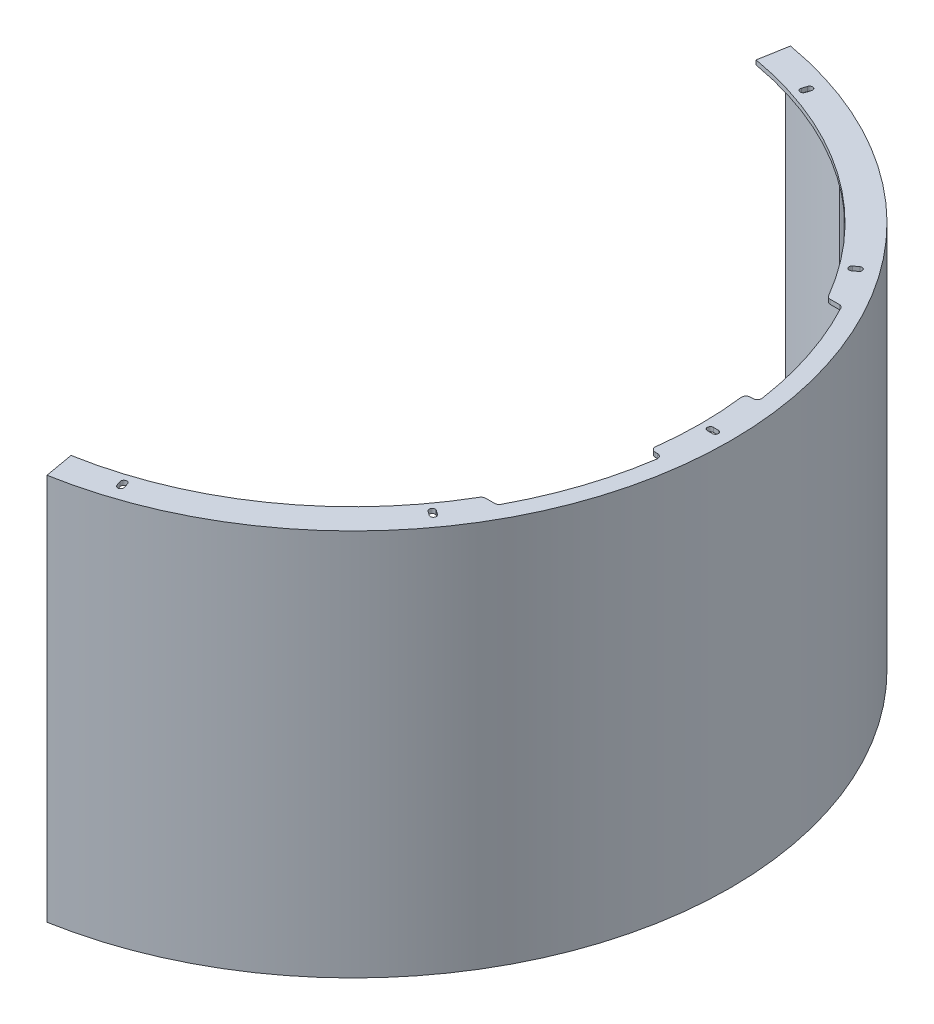
SolidWorks part; units mm, degrees
ref_plane "Front Plane" through (0, 0, 0) normal (0, 0, 1) x (1, 0, 0)
ref_plane "Top Plane" through (0, 0, 0) normal (0, 1, 0) x (1, 0, 0)
ref_plane "Right Plane" through (0, 0, 0) normal (1, 0, 0) x (0, 0, -1)
sketch "Sketch3" plane through (0, 0, 0) normal (0, 1, 0) x (1, 0, 0)
  line L0 (0, -251.5) -> (0, 251.5)
  line L1 (-44.1935, 250.6336) -> (-43.6725, 247.6791)
  line L2 (-43.6725, -247.6791) -> (-44.1935, -250.6336)
  arc A0 (0, 251.5) -> (0, -251.5) centre (0, 0) cw
  arc A1 (0, 251.5) -> (-43.6725, 247.6791) centre (0, 0) ccw
  arc A2 (0, -251.5) -> (-43.6725, -247.6791) centre (0, 0) cw
  arc A3 (0, 254.5) -> (0, -254.5) centre (0, 0) cw
  arc A4 (0, 254.5) -> (-44.1935, 250.6336) centre (0, 0) ccw
  arc A5 (0, -254.5) -> (-44.1935, -250.6336) centre (0, 0) cw
  point P4 (0, 0)
  dimension "D1" = 503
  dimension "D2" = 3
  dimension "D3" = 3
  dimension "D4" = 3
extrude "Boss-Extrude1" add sketch "Sketch3" along normal blind 255 contours A5 A3 A4 L1 A1 A0 A2 L2 region at (252.0902, 0, 0)
sketch "Sketch6" plane through (0, 255, 0) normal (0, 1, 0) x (1, 0, 0)
  line L0 (0, -256) -> (0, 256)
  line L1 (-2, 253.0819) -> (-2, 247.0819)
  line L2 (-1, 246.0819) -> (1, 246.0819)
  line L3 (2, 247.0819) -> (2, 253.0819)
  line L4 (-2, 253.0819) -> (2, 253.0819)
  line L54 (108.0062, 228.8867) -> (105.4029, 223.4809)
  line L55 (105.87, 222.146) -> (107.6719, 221.2783)
  line L56 (109.0068, 221.7454) -> (111.6101, 227.1512)
  line L57 (108.0062, 228.8867) -> (111.6101, 227.1512)
  line L58 (196.6204, 159.3577) -> (191.9294, 155.6167)
  line L59 (191.7711, 154.2114) -> (193.0181, 152.6477)
  line L60 (194.4234, 152.4894) -> (199.1144, 156.2303)
  line L61 (196.6204, 159.3577) -> (199.1144, 156.2303)
  line L62 (246.2916, 58.2659) -> (240.442, 56.9308)
  line L63 (239.6896, 55.7333) -> (240.1347, 53.7835)
  line L64 (241.3321, 53.031) -> (247.1817, 54.3662)
  line L65 (246.2916, 58.2659) -> (247.1817, 54.3662)
  line L66 (247.1817, -54.3662) -> (241.3321, -53.031)
  line L67 (240.1347, -53.7835) -> (239.6896, -55.7333)
  line L68 (240.442, -56.9308) -> (246.2916, -58.2659)
  line L69 (247.1817, -54.3662) -> (246.2916, -58.2659)
  line L70 (199.1144, -156.2303) -> (194.4234, -152.4894)
  line L71 (193.0181, -152.6477) -> (191.7711, -154.2114)
  line L72 (191.9294, -155.6167) -> (196.6204, -159.3577)
  line L73 (199.1144, -156.2303) -> (196.6204, -159.3577)
  line L74 (111.6101, -227.1512) -> (109.0068, -221.7454)
  line L75 (107.6719, -221.2783) -> (105.87, -222.146)
  line L76 (105.4029, -223.4809) -> (108.0062, -228.8867)
  line L77 (111.6101, -227.1512) -> (108.0062, -228.8867)
  line L78 (2, -253.0819) -> (2, -247.0819)
  line L79 (1, -246.0819) -> (-1, -246.0819)
  line L80 (-2, -247.0819) -> (-2, -253.0819)
  line L81 (2, -253.0819) -> (-2, -253.0819)
  arc A2 (2, 247.0819) -> (1, 246.0819) centre (1, 247.0819) cw
  arc A3 (-2, 247.0819) -> (-1, 246.0819) centre (-1, 247.0819) ccw
  arc A26 (109.0068, 221.7454) -> (107.6719, 221.2783) centre (108.1058, 222.1792) cw
  arc A27 (105.4029, 223.4809) -> (105.87, 222.146) centre (106.3039, 223.047) ccw
  arc A28 (194.4234, 152.4894) -> (193.0181, 152.6477) centre (193.7999, 153.2712) cw
  arc A29 (191.9294, 155.6167) -> (191.7711, 154.2114) centre (192.5529, 154.8349) ccw
  arc A30 (241.3321, 53.031) -> (240.1347, 53.7835) centre (241.1096, 54.006) cw
  arc A31 (240.442, 56.9308) -> (239.6896, 55.7333) centre (240.6645, 55.9558) ccw
  arc A32 (240.442, -56.9308) -> (239.6896, -55.7333) centre (240.6645, -55.9558) cw
  arc A33 (241.3321, -53.031) -> (240.1347, -53.7835) centre (241.1096, -54.006) ccw
  arc A34 (191.9294, -155.6167) -> (191.7711, -154.2114) centre (192.5529, -154.8349) cw
  arc A35 (194.4234, -152.4894) -> (193.0181, -152.6477) centre (193.7999, -153.2712) ccw
  arc A36 (105.4029, -223.4809) -> (105.87, -222.146) centre (106.3039, -223.047) cw
  arc A37 (109.0068, -221.7454) -> (107.6719, -221.2783) centre (108.1058, -222.1792) ccw
  arc A38 (-2, -247.0819) -> (-1, -246.0819) centre (-1, -247.0819) cw
  arc A39 (2, -247.0819) -> (1, -246.0819) centre (1, -247.0819) ccw
  point P9 (0, 0)
  point P19 (2, 246.0819)
  point P22 (-2, 246.0819)
  point P23 (0, 246.0819)
  point P59 (0, 0)
  point P68 (0, 0)
  point P76 (0, 0)
  dimension "D3" = 1
  dimension "D1" = 7
  dimension "D2" = 4
  dimension "D4" = 0
  dimension "D5" = 7
  dimension "D6" = 256
  dimension "D7" = 8
extrude "Boss-Extrude2" add sketch "Sketch6" against normal blind 255 separate body contours L3 L4 L1 A3 L2 A2 | L56 L57 L54 A27 L55 A26 | L60 L61 L58 A29 L59 A28 | L64 L65 L62 A31 L63 A30 | L68 L69 L66 A33 L67 A32 | L72 L73 L70 A35 L71 A34 | L76 L77 L74 A37 L75 A36 | L78 A39 L79 A38 L80 L81
combine bodies "Combine2" operation type add bodies to combine 109 101 115 116 117 118 119 120 121
sketch "Sketch7" plane through (0, 255, 0) normal (0, 1, 0) x (1, 0, 0)
  line L0 (-44.1935, 250.6336) -> (-40.7205, 230.9374)
  line L1 (-44.1935, -250.6336) -> (-40.7205, -230.9374)
  arc A0 (-40.7205, 230.9374) -> (-40.7205, -230.9374) centre (0, 0) cw
  arc A2 (-44.1935, 250.6336) -> (-44.1935, -250.6336) centre (0, 0) cw
  arc A3 (-44.1935, -250.6336) -> (-44.1935, 250.6336) centre (0, 0) ccw construction
extrude "Boss-Extrude3" add sketch "Sketch7" along normal blind 3 contours A2 L0 A0 L1 region at (248.5983, 255, 0)
sketch "Sketch8" plane through (0, 255, 0) normal (0, -1, 0) x (1, 0, 0)
  line L0 (240.8, 0) -> (244.2, 0) construction
  line L1 (240.8, 2) -> (244.2, 2)
  line L2 (240.8, -2) -> (244.2, -2)
  line L3 (194.8113, -141.5387) -> (197.562, -143.5372) construction
  line L12 (195.9869, -139.9207) -> (198.7375, -141.9191)
  line L21 (193.6357, -143.1567) -> (196.3864, -145.1552)
  line L24 (74.4113, -229.0144) -> (75.462, -232.248) construction
  line L27 (76.3134, -228.3964) -> (77.3641, -231.63)
  line L28 (72.5092, -229.6324) -> (73.5598, -232.866)
  line L29 (-74.4113, -229.0144) -> (-75.462, -232.248) construction
  line L30 (-72.5092, -229.6324) -> (-73.5598, -232.866)
  line L31 (-76.3134, -228.3964) -> (-77.3641, -231.63)
  line L32 (-194.8113, -141.5387) -> (-197.562, -143.5372) construction
  line L33 (-193.6357, -143.1567) -> (-196.3864, -145.1552)
  line L34 (-195.9869, -139.9207) -> (-198.7375, -141.9191)
  line L35 (-240.8, 0) -> (-244.2, 0) construction
  line L36 (-240.8, -2) -> (-244.2, -2)
  line L37 (-240.8, 2) -> (-244.2, 2)
  line L38 (-194.8113, 141.5387) -> (-197.562, 143.5372) construction
  line L39 (-195.9869, 139.9207) -> (-198.7375, 141.9191)
  line L40 (-193.6357, 143.1567) -> (-196.3864, 145.1552)
  line L41 (-74.4113, 229.0144) -> (-75.462, 232.248) construction
  line L42 (-76.3134, 228.3964) -> (-77.3641, 231.63)
  line L43 (-72.5092, 229.6324) -> (-73.5598, 232.866)
  line L44 (74.4113, 229.0144) -> (75.462, 232.248) construction
  line L45 (72.5092, 229.6324) -> (73.5598, 232.866)
  line L46 (76.3134, 228.3964) -> (77.3641, 231.63)
  line L47 (194.8113, 141.5387) -> (197.562, 143.5372) construction
  line L48 (193.6357, 143.1567) -> (196.3864, 145.1552)
  line L49 (195.9869, 139.9207) -> (198.7375, 141.9191)
  circle A1 centre (242.5, 0) radius 1.7 construction
  arc A2 (240.8, 2) -> (240.8, -2) centre (240.8, 0) ccw
  arc A3 (244.2, -2) -> (244.2, 2) centre (244.2, 0) ccw
  arc A24 (195.9869, -139.9207) -> (193.6357, -143.1567) centre (194.8113, -141.5387) ccw
  arc A25 (196.3864, -145.1552) -> (198.7375, -141.9191) centre (197.562, -143.5372) ccw
  arc A26 (76.3134, -228.3964) -> (72.5092, -229.6324) centre (74.4113, -229.0144) ccw
  arc A27 (73.5598, -232.866) -> (77.3641, -231.63) centre (75.462, -232.248) ccw
  arc A28 (-72.5092, -229.6324) -> (-76.3134, -228.3964) centre (-74.4113, -229.0144) ccw
  arc A29 (-77.3641, -231.63) -> (-73.5598, -232.866) centre (-75.462, -232.248) ccw
  arc A30 (-193.6357, -143.1567) -> (-195.9869, -139.9207) centre (-194.8113, -141.5387) ccw
  arc A31 (-198.7375, -141.9191) -> (-196.3864, -145.1552) centre (-197.562, -143.5372) ccw
  arc A32 (-240.8, -2) -> (-240.8, 2) centre (-240.8, 0) ccw
  arc A33 (-244.2, 2) -> (-244.2, -2) centre (-244.2, 0) ccw
  arc A34 (-195.9869, 139.9207) -> (-193.6357, 143.1567) centre (-194.8113, 141.5387) ccw
  arc A35 (-196.3864, 145.1552) -> (-198.7375, 141.9191) centre (-197.562, 143.5372) ccw
  arc A36 (-76.3134, 228.3964) -> (-72.5092, 229.6324) centre (-74.4113, 229.0144) ccw
  arc A37 (-73.5598, 232.866) -> (-77.3641, 231.63) centre (-75.462, 232.248) ccw
  arc A38 (72.5092, 229.6324) -> (76.3134, 228.3964) centre (74.4113, 229.0144) ccw
  arc A39 (77.3641, 231.63) -> (73.5598, 232.866) centre (75.462, 232.248) ccw
  arc A40 (193.6357, 143.1567) -> (195.9869, 139.9207) centre (194.8113, 141.5387) ccw
  arc A41 (198.7375, 141.9191) -> (196.3864, 145.1552) centre (197.562, 143.5372) ccw
  point P6 (242.5, 0)
  point P16 (196.1866, -142.5379)
  point P23 (74.9366, -230.6312)
  point P28 (0, 0)
  point P31 (-74.9366, -230.6312)
  point P35 (0, 0)
  point P39 (-196.1866, -142.5379)
  point P44 (0, 0)
  point P47 (-242.5, 0)
  point P54 (-196.1866, 142.5379)
  point P57 (0, 0)
  point P62 (-74.9366, 230.6312)
  point P69 (74.9366, 230.6312)
  point P76 (196.1866, 142.5379)
  point P81 (0, 0)
  dimension "D1" = 2
extrude "Cut-Extrude3" cut sketch "Sketch8" against normal blind 5
pattern_linear "LPattern1" count 2 spacing 258 along (0, -1, 0) of "Boss-Extrude3"
pattern_linear "LPattern2" count 2 spacing 258 along (0, -1, 0) of "Cut-Extrude3"
sketch "Sketch11" plane through (0, 258, 0) normal (0, 1, 0) x (1, 0, 0)
  line L0 (-44.1935, 250.6336) -> (0, 0)
  line L1 (0, 0) -> (44.1935, 250.6336)
  line L2 (-117.5787, 0) -> (117.5787, 0) construction
  arc A0 (-44.1935, 250.6336) -> (44.1935, 250.6336) centre (0, 0) cw
extrude "Cut-Extrude7" cut sketch "Sketch11" against normal blind 324
mirror "Mirror1" about plane through (0, 0, 0) normal (0, 0, 1) of "Cut-Extrude7"
sketch "Sketch13" plane through (0, 258, 0) normal (0, 1, 0) x (1, 0, 0)
  line L3 (240.8, 32.1355) -> (189.8429, 32.1355)
  line L4 (189.8429, 32.1355) -> (189.8429, 116.171)
  line L5 (189.8429, 116.171) -> (213.358, 116.171)
  line L6 (-117.5787, 0) -> (117.5787, 0) construction
  line L7 (189.8429, -116.171) -> (213.358, -116.171)
  line L8 (189.8429, -32.1355) -> (189.8429, -116.171)
  line L9 (240.8, -32.1355) -> (189.8429, -32.1355)
  arc A0 (240.8, 32.1355) -> (213.358, 116.171) centre (0, 0) ccw
  arc A1 (240.8, -32.1355) -> (213.358, -116.171) centre (0, 0) cw
extrude "Cut-Extrude10" cut sketch "Sketch13" against normal blind 5
fillet "Fillet2" radius 3 8 edges at (203.7021, 256.5, 116.171) (213.358, 256.5, 116.171) (232.2877, 256.5, 32.1355) (240.8, 256.5, 32.1355) (232.2877, 256.5, -32.1355) (240.8, 256.5, -32.1355) (213.358, 256.5, -116.171) (203.7021, 256.5, -116.171)
